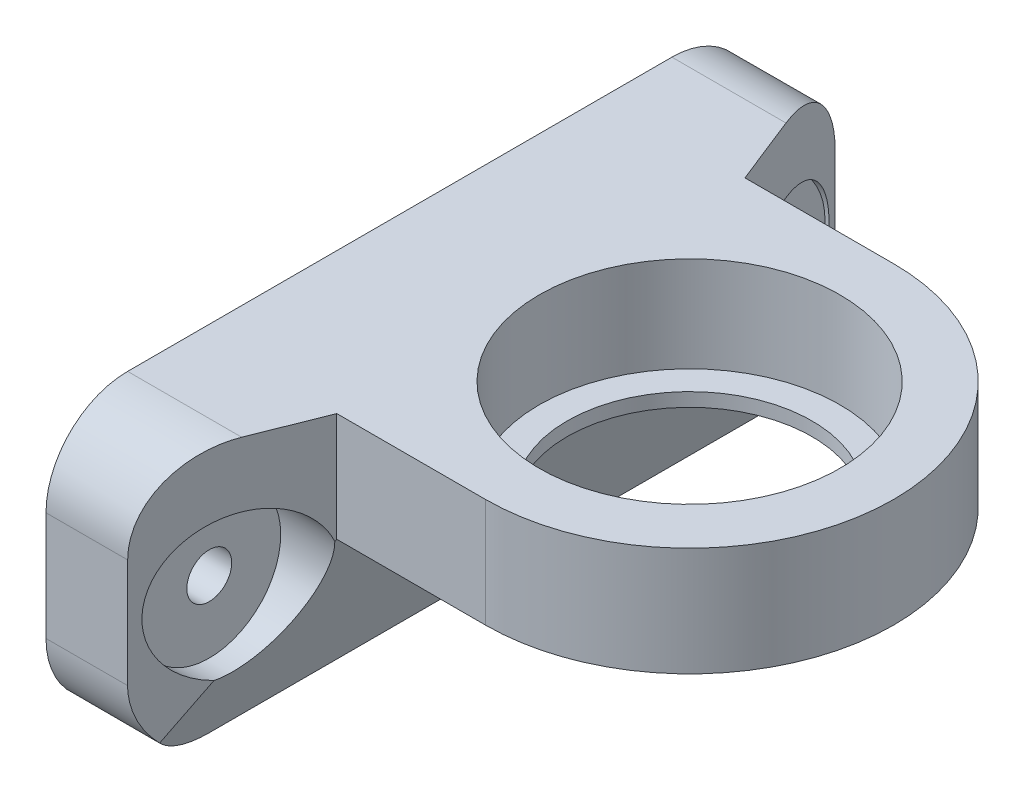
SolidWorks part; units mm, degrees
ref_plane "Plano frontal" through (0, 0, 0) normal (0, 0, 1) x (1, 0, 0)
ref_plane "Plano superior" through (0, 0, 0) normal (0, 1, 0) x (1, 0, 0)
ref_plane "Plano direito" through (0, 0, 0) normal (1, 0, 0) x (0, 0, -1)
sketch "Esboço1" plane through (0, 0, 0) normal (0, 0, 1) x (1, 0, 0)
  line L0 (0, 0) -> (6, 0)
  line L1 (49, 12) -> (49, 20)
  line L2 (49, 20) -> (0, 20)
  line L3 (6, 0) -> (10.3676, 12)
  line L5 (0, 20) -> (0, 0)
  line L7 (10.3676, 12) -> (49, 12)
  dimension "D1" = 20
  dimension "D2" = 8
  dimension "D3" = 6
  dimension "D4" = 20
extrude "Ressalto-extrusão1" add sketch "Esboço1" along normal blind 60
sketch "Esboço2" plane through (0, 12, 0) normal (0, -1, 0) x (1, 0, 0)
  line L1 (0, 60) -> (6, 60) construction
  line L2 (49, 60) -> (49, 0) construction
  line L3 (0, 60) -> (0, 0) construction
  line L4 (21.3, 15) -> (10.3676, 15)
  line L5 (10.3676, 45) -> (6, 56)
  line L6 (0, 4) -> (0, 0)
  line L7 (0, 0) -> (49, 0)
  line L8 (49, 0) -> (49, 60)
  line L9 (49, 60) -> (0, 60)
  line L10 (0, 60) -> (0, 56)
  line L11 (10.3676, 45) -> (21.3, 45)
  line L14 (10.3676, 60) -> (10.3676, 0) construction
  line L15 (6, 60) -> (6, 0) construction
  line L16 (6, 56) -> (0, 56)
  line L17 (49, 30) -> (-2.2635, 30) construction
  line L18 (6, 4) -> (0, 4)
  line L19 (10.3676, 15) -> (6, 4)
  circle A1 centre (21.3, 30) radius 9
  arc A2 (21.3, 15) -> (21.3, 45) centre (21.3, 30) ccw
  point P16 (49, 30)
  dimension "D1" = 18
  dimension "D2" = 21.3
  dimension "D3" = 30
  dimension "D4" = 52
extrude "Corte-extrusão1" cut sketch "Esboço2" against normal through all both and the other way through all
sketch "Esboço3" plane through (0, 0, 0) normal (-1, 0, 0) x (0, 0, 1)
  line L0 (56, 0) -> (4, 0) construction
  line L1 (45, 20) -> (15, 20) construction
  line L2 (30, 20) -> (30, 0) construction
  circle A0 centre (50, 10) radius 1.65
  circle A1 centre (10, 10) radius 1.65
  dimension "D1" = 3.3
  dimension "D2" = 10
  dimension "D3" = 40
extrude "Corte-extrusão2" cut sketch "Esboço3" against normal through all
sketch "Esboço4" plane through (0, 20, 0) normal (0, 1, 0) x (1, 0, 0)
  circle A0 centre (21.3, -30) radius 11.05
  dimension "D1" = 22.1
extrude "Corte-extrusão3" cut sketch "Esboço4" against normal blind 7
sketch "Esboço7" plane through (0, 0, 0) normal (1, 0, 0) x (0, 0, -1)
  circle A0 centre (-50, 10) radius 5.25
  circle A1 centre (-10, 10) radius 5.25
  dimension "D1" = 10.5
extrude "Corte-extrusão5" cut sketch "Esboço7" along normal blind 10 from offset 6
extrude "Corte-extrusão7" cut sketch "Esboço7<2>" along normal blind 1
sketch "Esboço7<2>" plane through (0, 0, 0) normal (1, 0, 0) x (0, 0, -1) same geometry as "Esboço7"
fillet "Filete1" radius 6 4 edges at (3, 0, 4) (3, 20, 4) (3, 20, 56) (3, 0, 56)
